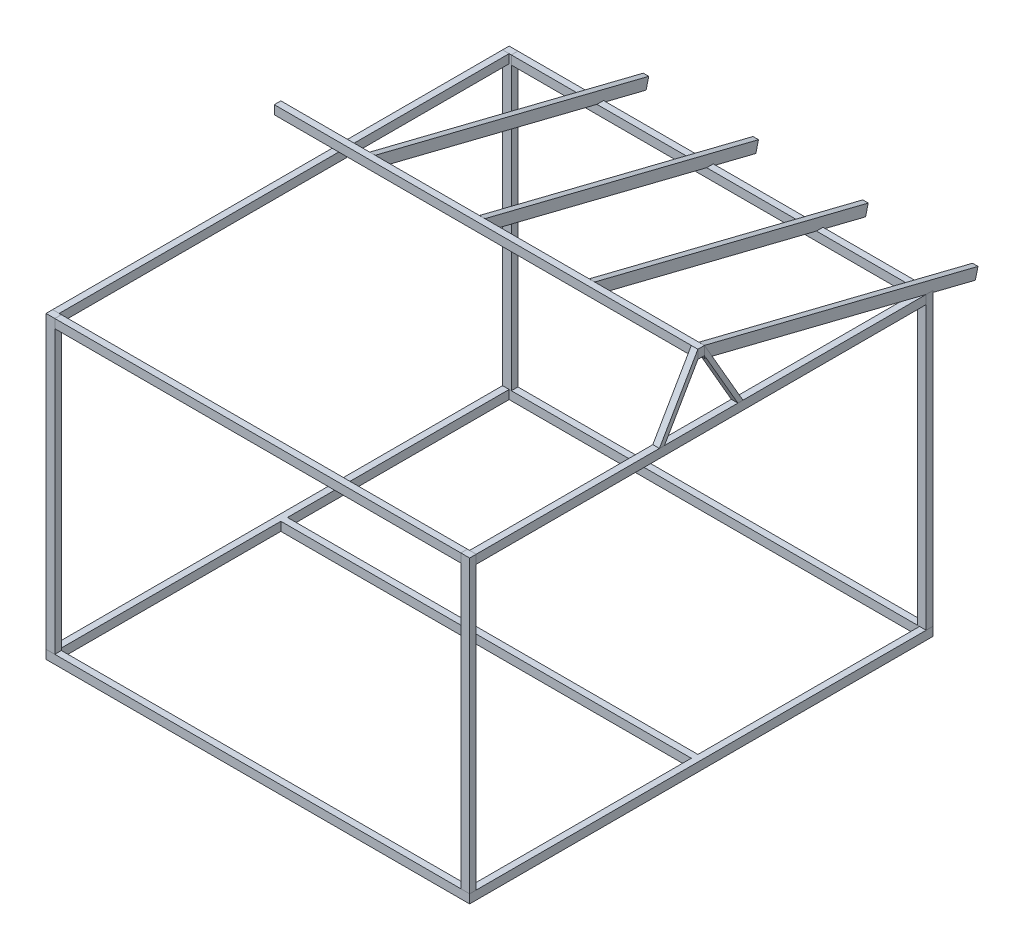
SolidWorks part; units mm, degrees
ref_plane "Front Plane" through (0, 0, 0) normal (0, 0, 1) x (1, 0, 0)
ref_plane "Top Plane" through (0, 0, 0) normal (0, 1, 0) x (1, 0, 0)
ref_plane "Right Plane" through (0, 0, 0) normal (1, 0, 0) x (0, 0, -1)
other "Configuration Table"
sketch "MetalBase" plane through (0, 0, 0) normal (0, 1, 0) x (1, 0, 0)
  line L0 (-60, -60) -> (7660, -60)
  line L1 (0, 0) -> (7600, 0)
  line L2 (0, 0) -> (0, 2020)
  line L3 (0, 4100) -> (7600, 4100)
  line L4 (7600, 0) -> (7600, 2020)
  line L5 (7660, -60) -> (7660, 4160)
  line L6 (-60, 4160) -> (7660, 4160)
  line L7 (-60, -60) -> (-60, 4160)
  line L8 (0, 2050) -> (7600, 2050) construction
  line L9 (0, 2020) -> (7600, 2020)
  line L10 (0, 2080) -> (7600, 2080)
  line L11 (0, 2080) -> (0, 4100)
  line L12 (7600, 2080) -> (7600, 4100)
  line L13 (0, 0) -> (0, 4100) construction
  line L15 (7600, 0) -> (7600, 4100) construction
  point P15 (7660, 2050)
  dimension "D1" = 4100
  dimension "D2" = 7600
  dimension "D6" = 4220
  dimension "D7" = 7720
  dimension "D3" = 60
  dimension "D4" = 30
  dimension "D5" = 30
sketch "InternalSpace" plane through (0, 0, 0) normal (0, 1, 0) x (1, 0, 0)
  line L26 (50, 50) -> (7550, 50)
  line L27 (7550, 50) -> (7550, 4050)
  line L28 (7550, 4050) -> (50, 4050)
  line L29 (50, 4050) -> (50, 50)
  line L30 (50, 50) -> (7550, 50)
  line L31 (7550, 50) -> (7550, 4050)
  line L32 (7550, 4050) -> (50, 4050)
  line L33 (50, 4050) -> (50, 50)
  dimension "D2" = 4000
  dimension "D3" = 7500
  dimension "D1" = 110
sketch "Furniture" plane through (0, 0, 0) normal (0, 1, 0) x (1, 0, 0)
  line L0 (6750, 2050) -> (6750, 4050)
  line L1 (2200, 2550) -> (1400, 2550)
  line L2 (2200, 2550) -> (2200, 4050)
  line L3 (2200, 4050) -> (1400, 4050)
  line L4 (1400, 2550) -> (1400, 4050)
  line L5 (1050, 50) -> (50, 50)
  line L6 (1050, 50) -> (1050, 2050)
  line L7 (1050, 2050) -> (50, 2050)
  line L8 (50, 50) -> (50, 2050)
  line L9 (6350, 2110) -> (7550, 2110)
  line L10 (2200, 4050) -> (2200, 150)
  line L11 (0, 0) -> (7600, 0) construction
  line L12 (6350, 50) -> (6350, 2110)
  line L13 (6470, 50) -> (6470, 1990)
  line L15 (2200, 2050) -> (7550, 2050) construction
  line L17 (1979.5569, 919.0285) -> (2200, 150)
  line L18 (6350, 150) -> (5722.0427, 459.305)
  line L19 (6710, 1120.0467) -> (7310, 1120.0467)
  line L24 (6710, 1120.0467) -> (6710, 1880.0467)
  line L25 (6710, 1880.0467) -> (7310, 1880.0467)
  line L26 (7310, 1120.0467) -> (7310, 1880.0467)
  line L27 (6350, 2110) -> (5750, 2110)
  line L28 (6350, 2110) -> (6350, 1510)
  line L29 (6350, 1510) -> (5750, 1510)
  line L30 (5750, 2110) -> (5750, 1510)
  line L31 (2320, 2050) -> (4320, 2050) construction
  line L32 (4320, 2050) -> (4320, 4050) construction
  line L33 (2200, 150) -> (2499.3532, 150) construction
  line L34 (2499.3532, 150) -> (2499.3532, 981.1813) construction
  line L35 (2499.3532, 981.1813) -> (2200, 981.1813) construction
  line L36 (2320, 4050) -> (2320, 150)
  line L37 (2200, 150) -> (2200, 50)
  line L38 (50, 50) -> (7550, 50) construction
  line L39 (2320, 150) -> (2320, 50)
  line L40 (7550, 4050) -> (50, 4050) construction
  line L41 (7550, 50) -> (7550, 4050) construction
  line L42 (50, 4050) -> (50, 50) construction
  line L43 (7550, 4050) -> (50, 4050) construction
  line L44 (7550, 50) -> (7550, 4050) construction
  line L45 (50, 50) -> (7550, 50) construction
  line L46 (50, 4050) -> (50, 50) construction
  line L47 (7010, 1120.0467) -> (7010, 1445.9123) construction
  line L48 (6470, 1990) -> (7550, 1990)
  line L49 (-60, -60) -> (-60, 4160) construction
  line L50 (7550, 809.8905) -> (7383.7397, 809.8905)
  line L51 (7550, 809.8905) -> (7550, 230.8186)
  line L52 (7550, 230.8186) -> (7383.7397, 230.8186)
  line L53 (7283.7397, 709.8905) -> (7283.7397, 330.8186)
  line L54 (7660, 4160) -> (-60, 4160) construction
  line L55 (-60, 4160) -> (-60, -60) construction
  line L56 (-60, -60) -> (7660, -60) construction
  line L57 (7660, -60) -> (7660, 4160) construction
  arc A1 (1979.5569, 919.0285) -> (1414.1883, 0) centre (2200, 150) ccw construction
  arc A2 (5722.0427, 459.305) -> (6350, 850) centre (6350, 150) cw construction
  arc A3 (7383.7397, 230.8186) -> (7283.7397, 330.8186) centre (7383.7397, 330.8186) cw
  arc A4 (7383.7397, 809.8905) -> (7283.7397, 709.8905) centre (7383.7397, 709.8905) ccw
  point P56 (7010, 1990)
  dimension "D13" = 600
  dimension "D21" = 100
  dimension "D1" = 1500
  dimension "D2" = 800
  dimension "D3" = 2000
  dimension "D4" = 1000
  dimension "D5" = 100
  dimension "D6" = 60
  dimension "D7" = 700
  dimension "D8" = 600
  dimension "D9" = 2260
  dimension "D10" = 800
  dimension "D11" = 100
  dimension "D12" = 760
  dimension "D14" = 2000
  dimension "D15" = 800
  dimension "D16" = 2000
  dimension "D17" = 600
  dimension "D18" = 60
  dimension "D19" = 4150
  dimension "D20" = 120
  dimension "D22" = 120
  dimension "D23" = 110
  dimension "D25" = 4220
  dimension "D26" = 1200
  dimension "D27" = 4030
  dimension "D24" = 110
sketch "Metal frame" plane through (0, 0, 0) normal (0, 1, 0) x (1, 0, 0)
  line L0 (0, 4100) -> (7600, 4100) construction
  line L1 (0, 4100) -> (7600, 4100)
  line L3 (0, 0) -> (0, 2020)
  line L4 (0, 0) -> (7600, 0) construction
  line L5 (0, 0) -> (7600, 0)
  line L7 (7600, 0) -> (7600, 2020)
  line L8 (-60, 4160) -> (7660, 4160)
  line L9 (7660, -60) -> (7660, 4160)
  line L10 (-60, -60) -> (7660, -60)
  line L11 (-60, -60) -> (-60, 4160)
  line L12 (0, 2050) -> (62.1159, 2050) construction
  line L13 (7600, 2080) -> (0, 2080)
  line L15 (7600, 2020) -> (0, 2020)
  line L17 (7600, 2080) -> (7600, 4100)
  line L18 (0, 2080) -> (0, 4100)
  line L19 (7600, 0) -> (7600, 4100) construction
  line L21 (0, 0) -> (0, 4100) construction
  point P14 (-60, 2050)
  dimension "D2" = 7720
  dimension "D3" = 4220
  dimension "D4" = 60
  dimension "D1" = 60
sketch "Walls bottom" plane through (0, 0, 0) normal (0, 1, 0) x (1, 0, 0)
  line L0 (-60, 4160) -> (7660, 4160) construction
  line L2 (-60, -60) -> (7660, -60) construction
  line L3 (7660, -60) -> (7660, 4160) construction
  line L4 (-60, -60) -> (-60, 4160) construction
  line L5 (-60, -60) -> (7660, -60)
  line L6 (7660, -60) -> (7660, 4160)
  line L7 (-60, 4160) -> (7660, 4160)
  line L8 (-60, -60) -> (-60, 4160)
  line L9 (40, 40) -> (40, 4060)
  line L10 (40, 4060) -> (7560, 4060)
  line L11 (7560, 40) -> (7560, 4060)
  line L12 (40, 40) -> (7560, 40)
  dimension "D2" = 4020
  dimension "D3" = 7520
  dimension "D4" = 7720
  dimension "D5" = 4220
  dimension "D1" = 100
sketch "Sketch15" plane through (0, 0, 0) normal (0, 1, 0) x (1, 0, 0)
  line L2 (7550, 50) -> (5502.4266, 50)
  line L3 (7550, 50) -> (7550, 1250)
  line L4 (7550, 1250) -> (5502.4266, 1250)
  line L5 (5502.4266, 50) -> (5502.4266, 1250)
  dimension "D1" = 1200
extrude "MetalFrame" add sketch "Metal frame" against normal blind 80 contours L11 L10 L9 L8 L15 L7 L5 L3 L13 L18 L1 L17 region at (3800, 0, -2050)
sketch "Sketch18" plane through (0, 0, 0) normal (0, 1, 0) x (1, 0, 0)
  line L0 (0, 0) -> (7600, 0) construction
  line L1 (3800, -1014.8769) -> (8467.9433, -1014.8769)
  line L2 (3800, -1014.8769) -> (3800, 5493.3133)
  line L3 (3800, 5493.3133) -> (8467.9433, 5493.3133)
  line L4 (8467.9433, -1014.8769) -> (8467.9433, 5493.3133)
  point P6 (3800, 0)
extrude "Cut-Extrude1" cut sketch "Sketch18" against normal through all
sketch "Sketch19" plane through (0, 0, 0) normal (0, 1, 0) x (1, 0, 0)
  line L0 (0, 0) -> (3800, 0) construction
  line L1 (3800, 4100) -> (3740, 4100)
  line L2 (3800, 4100) -> (3800, 0)
  line L3 (3800, 0) -> (3740, 0)
  line L4 (3740, 4100) -> (3740, 0)
  dimension "D1" = 60
extrude "Boss-Extrude1" add sketch "Sketch19" against normal blind 80
sketch "Roof" plane through (0, 0, 0) normal (1, 0, 0) x (0, 0, -1)
  line L0 (2050, 0) -> (2050, 3177.5) construction
  line L1 (4160, 0) -> (-60, 0) construction
  line L2 (4160, 0) -> (4160, 2650) construction
  line L3 (4160, 2650) -> (2050, 3177.5) construction
  line L4 (2050, 3177.5) -> (5424.8088, 3177.5) construction
  line L5 (4160, 2650) -> (4548.057, 2552.9857) construction
  line L6 (4160, 150) -> (-211.81, 150) construction
  line L7 (4160, 2650) -> (2960, 2650)
  line L8 (2960, 2650) -> (2960, 2950)
  dimension "D1" = 2500
  dimension "D2" = 1200
  dimension "D3" = 150
  dimension "D4" = 2174.9382
  dimension "D5" = 400
  dimension "D6" = 2574.9382
  dimension "D7" = 2650
  dimension "D8" = 300
  dimension "D9" = 3027.5
  dimension "D10" = 14.036
sketch "Sketch23" plane through (-60, 0, 0) normal (1, 0, 0) x (0, 0, -1)
  line L0 (2050, 0) -> (2050, 3177.5) construction
  line L1 (4160, 0) -> (4100, 0)
  line L2 (4160, 0) -> (4160, 2650)
  line L3 (4160, 2650) -> (4100, 2650)
  line L4 (4100, 0) -> (4100, 2650)
  line L5 (0, 0) -> (0, 2650)
  line L6 (-60, 2650) -> (0, 2650)
  line L7 (-60, 0) -> (-60, 2650)
  line L8 (-60, 0) -> (0, 0)
  line L10 (0, 2650) -> (4100, 2650)
  line L11 (0, 2650) -> (0, 2570)
  line L12 (0, 2570) -> (4100, 2570)
  line L13 (4100, 2650) -> (4100, 2570)
  line M8 (-60, 0) -> (4160, 0)
  dimension "D1" = 60
  dimension "D2" = 80
extrude "Boss-Extrude5" add sketch "Sketch23" along normal blind 80 separate body contours L4 L3 L2 M8 | L7 L6 L5 M8 region at (-60, 1325, -4130) region at (-60, 1325, 30)
extrude "Boss-Extrude6" add sketch "Sketch23<3>" along normal blind 60 separate body contours L0 L12 L5 L10 | L12 L0 L10 L4 region at (-60, 2610, -1025) region at (-60, 2610, -3075)
sketch "Sketch23<3>" plane through (-60, 0, 0) normal (1, 0, 0) x (0, 0, -1) same geometry as "Sketch23"
extrude "Boss-Extrude7" add sketch "Sketch23<5>" against normal blind 80 from surface separate body contours L4 L3 L2 M8 | L7 L6 L5 M8 region at (-60, 1325, -4130) region at (-60, 1325, 30) starting at face at (3800, -40, -2050)
sketch "Sketch23<5>" plane through (-60, 0, 0) normal (1, 0, 0) x (0, 0, -1) same geometry as "Sketch23"
extrude "Boss-Extrude8" add sketch "Sketch23<6>" against normal blind 60 from surface separate body contours L12 L0 L10 L4 | L0 L12 L5 L10 region at (-60, 2610, -1025) region at (-60, 2610, -3075) starting at face at (3800, 1325, 30)
sketch "Sketch23<6>" plane through (-60, 0, 0) normal (1, 0, 0) x (0, 0, -1) same geometry as "Sketch23"
sketch "Sketch24" plane through (0, 2650, 0) normal (0, 1, 0) x (1, 0, 0)
  line L1 (20, 4160) -> (3720, 4160)
  line L2 (20, 4160) -> (20, 4100)
  line L3 (20, 4100) -> (3720, 4100)
  line L4 (3720, 4160) -> (3720, 4100)
  line L5 (20, 0) -> (3720, 0)
  line L6 (20, 0) -> (20, -60)
  line L7 (20, -60) -> (3720, -60)
  line L8 (3720, 0) -> (3720, -60)
extrude "Boss-Extrude9" add sketch "Sketch24" against normal blind 80 separate body
sketch "Sketch25" plane through (3800, 0, 0) normal (1, 0, 0) x (0, 0, -1)
  line L0 (2050, 3177.5) -> (5424.8088, 3177.5) construction
  line L1 (2020, 3257.5) -> (2080, 3257.5)
  line L2 (2020, 3257.5) -> (2020, 3177.5)
  line L3 (2020, 3177.5) -> (2080, 3177.5)
  line L4 (2080, 3257.5) -> (2080, 3177.5)
  line L5 (2020, 3177.5) -> (1715.4477, 2650)
  line L6 (0, 2650) -> (4100, 2650) construction
  line L7 (2020, 3257.5) -> (1669.2597, 2650)
  line L8 (2050, 3177.5) -> (2050, 2907.5208) construction
  line L9 (2050, 0) -> (2050, 3177.5) construction
  line L10 (2080, 3177.5) -> (2384.5523, 2650)
  line L11 (2080, 3257.5) -> (2430.7403, 2650)
  point P6 (2050, 3177.5)
  line M8 (4100, 2650) -> (0, 2650)
  dimension "D1" = 60
  dimension "D2" = 80
  dimension "D3" = 40
extrude "Boss-Extrude10" add sketch "Sketch25" against normal blind 60 separate body contours L2 L7 L5 M8 | L11 L4 L10 M8 region at (3800, 2934.2199, -1855.9056) region at (3800, 2934.2199, -2244.0944)
extrude "Boss-Extrude11" add sketch "Sketch25<3>" against normal up to surface (3860 mm away) separate body contours L4 L1 L2 L3 region at (3800, 3217.5, -2050) up to face at (-60, 2610, -2050)
sketch "Sketch25<3>" plane through (3800, 0, 0) normal (1, 0, 0) x (0, 0, -1) same geometry as "Sketch25"
sketch "Sketch26" plane through (3800, 0, 0) normal (1, 0, 0) x (0, 0, -1)
  line L0 (4548.057, 2537.9857) -> (4160, 2635)
  line L1 (4548.057, 2537.9857) -> (4572.3106, 2635)
  line L3 (4572.3106, 2635) -> (2080, 3258.0776)
  line L4 (4100, 2635) -> (4100, 2650) construction
  line L5 (4100, 2650) -> (4160, 2650)
  line L6 (4160, 2650) -> (4160, 2635)
  line L7 (2080, 3155) -> (2080, 3258.0776)
  line L8 (4100, 2650) -> (2080, 3155)
  dimension "D1" = 100
extrude "Boss-Extrude12" add sketch "Sketch26" against normal blind 50 separate body
pattern_linear "LPattern1" count 4 spacing 1000 along (-1, 0, 0) of bodies 346
sketch "Sketch27" plane through (3800, 0, 0) normal (1, 0, 0) x (0, 0, -1)
  line L0 (2020, 3177.5) -> (2020, 2650)
  line L1 (0, 2650) -> (4100, 2650) construction
  line L2 (2080, 3155) -> (2080, 2650)
  line L3 (2050, 2650) -> (2050, 3180)
  line L4 (2050, 0) -> (2050, 3177.5) construction
  dimension "D1" = 527.5
  dimension "D2" = 505
  dimension "D3" = 530
